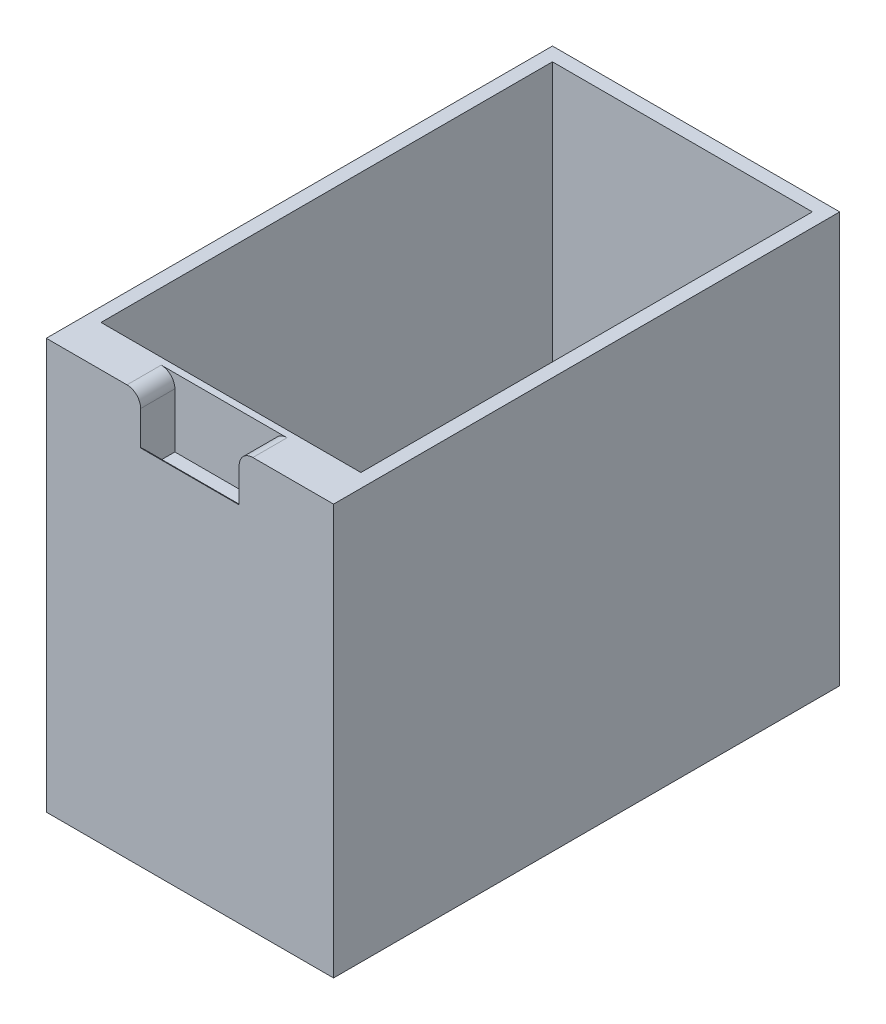
SolidWorks part; units mm, degrees
ref_plane "Plan de face" through (0, 0, 0) normal (0, 0, 1) x (1, 0, 0)
ref_plane "Plan de dessus" through (0, 0, 0) normal (0, 1, 0) x (1, 0, 0)
ref_plane "Plan de droite" through (0, 0, 0) normal (1, 0, 0) x (0, 0, -1)
sketch "Esquisse1" plane through (0, 0, 0) normal (0, 0, 1) x (1, 0, 0)
  line L1 (-113.8832, 42.5526) -> (96.1168, 42.5526)
  line L2 (-113.8832, 42.5526) -> (-113.8832, -257.4474)
  line L3 (-113.8832, -257.4474) -> (96.1168, -257.4474)
  line L4 (96.1168, 42.5526) -> (96.1168, -257.4474)
  dimension "D1" = 210
  dimension "D2" = 300
extrude "Boss.-Extru.1" add sketch "Esquisse1" against normal blind 370
sketch "Esquisse2" plane through (0, 42.5526, 0) normal (0, 1, 0) x (1, 0, 0)
  line L0 (-113.8832, 370) -> (-113.8832, 0) construction
  line L1 (-103.8832, 360) -> (86.1168, 360)
  line L2 (-103.8832, 360) -> (-103.8832, 30)
  line L3 (-103.8832, 30) -> (86.1168, 30)
  line L4 (86.1168, 360) -> (86.1168, 30)
  line L5 (96.1168, 370) -> (-113.8832, 370) construction
  line L6 (96.1168, 370) -> (96.1168, 0) construction
  line L7 (96.1168, 0) -> (-113.8832, 0) construction
  dimension "D1" = 10
  dimension "D2" = 10
  dimension "D3" = 10
  dimension "D4" = 30
extrude "Enlèv. mat.-Extru.1" cut sketch "Esquisse2" against normal blind 280
sketch "Esquisse5" plane through (0, 42.5526, 0) normal (0, 1, 0) x (1, 0, 0)
  line L0 (96.1168, 0) -> (-113.8832, 0) construction
  line L1 (27.1168, 0) -> (-44.8832, 0)
  line L2 (27.1168, 0) -> (27.1168, 25)
  line L3 (27.1168, 25) -> (-44.8832, 25)
  line L4 (-44.8832, 0) -> (-44.8832, 25)
  line L5 (96.1168, 370) -> (96.1168, 0) construction
  dimension "D1" = 72
  dimension "D2" = 25
  dimension "D3" = 69
extrude "Enlèv. mat.-Extru.4" cut sketch "Esquisse5" against normal blind 35
sketch "Esquisse6" plane through (0, 7.5526, 0) normal (0, 1, 0) x (1, 0, 0)
  line L0 (27.1168, 0) -> (27.1168, 25) construction
  line L1 (27.1168, 5) -> (-44.8832, 5)
  line L2 (27.1168, 5) -> (27.1168, 25)
  line L3 (27.1168, 25) -> (-44.8832, 25)
  line L4 (-44.8832, 5) -> (-44.8832, 25)
  line L5 (-44.8832, 0) -> (27.1168, 0) construction
  dimension "D1" = 5
extrude "Enlèv. mat.-Extru.5" cut sketch "Esquisse6" against normal blind 15
fillet "Congé5" radius 10 1 edges at (27.1168, 42.5526, -12.5)
fillet "Congé6" radius 10 1 edges at (-44.8832, 42.5526, -12.5)
fillet "Congé7" radius 10 1 edges at (-8.8832, 7.5526, -5)
